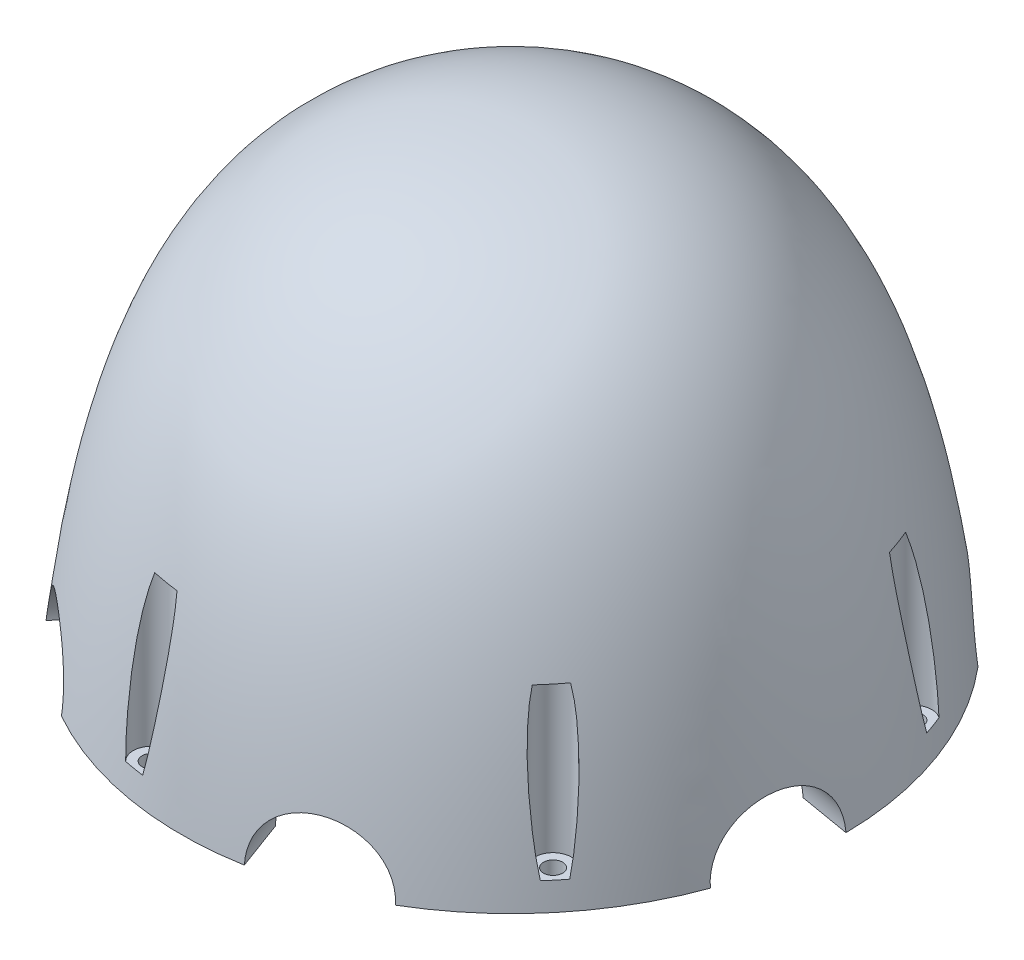
SolidWorks part; units mm, degrees
material "ABS"
ref_plane "前视基准面" through (0, 0, 0) normal (0, 0, 1) x (1, 0, 0)
ref_plane "上视基准面" through (0, 0, 0) normal (0, 1, 0) x (1, 0, 0)
ref_plane "右视基准面" through (0, 0, 0) normal (1, 0, 0) x (0, 0, -1)
sketch "草图1" plane through (0, 0, 0) normal (0, 0, 1) x (1, 0, 0)
  line L0 (-48.26, 0) -> (-57.15, 0)
  line L1 (0, 0) -> (0, 72.2657) construction
  line L2 (0, 72.2657) -> (0, 77.3457)
  line L3 (0, 77.3457) -> (27.4908, 77.3457) construction
  line L4 (0, 72.2657) -> (31.1413, 72.2657) construction
  spline S0 degree 3 poles (-48.26, 0) (-46.12, 40.7628) (-36.8511, 72.2657) (0, 72.2657) knots 0 0 0 0 1 1 1 1
  spline S1 degree 3 poles (-57.15, 0) (-53.2726, 34.209) (-44.696, 77.3457) (0, 77.3457) knots 0 0 0 0 1 1 1 1
  dimension "D3" = 5.08
  dimension "D1" = 114.3
  dimension "D2" = 8.89
revolve "旋转1" add sketch "草图1" angle 360 about L1
ref_plane "基准面1" through (0, 30.48, 0) normal (0, -1, 0) x (-1, 0, 0)
sketch "草图2" plane through (0, 30.48, 0) normal (0, -1, 0) x (-1, 0, 0)
  circle A0 centre (41.5481, 34.4537) radius 1.651
  circle A2 centre (50.6118, -18.7548) radius 1.651
  circle A3 centre (9.0637, -53.2085) radius 1.651
  circle A4 centre (-41.5481, -34.4537) radius 1.651
  circle A5 centre (-50.6118, 18.7548) radius 1.651
  circle A6 centre (-9.0637, 53.2085) radius 1.651
  point P17 (0, 0)
  dimension "D1" = 3.302
  dimension "D2" = 53.975
  dimension "D3" = 6
extrude "切除-拉伸2" cut sketch "草图2" along normal through all
sketch "草图3" plane through (0, 30.48, 0) normal (0, -1, 0) x (-1, 0, 0)
  circle A0 centre (41.5481, 34.4537) radius 3.175
  circle A2 centre (50.6118, -18.7548) radius 3.175
  circle A3 centre (9.0637, -53.2085) radius 3.175
  circle A4 centre (-41.5481, -34.4537) radius 3.175
  circle A6 centre (-50.6118, 18.7548) radius 3.175
  circle A7 centre (-9.0637, 53.2085) radius 3.175
  point P14 (16.2422, 43.8311)
  point P20 (0, 0)
  dimension "D1" = 6.35
  dimension "D2" = 53.975
  dimension "D3" = 6
extrude "切除-拉伸3" cut sketch "草图3" along normal blind 26
ref_axis "基准轴1" through (-50.6118, 4.48, 18.7548) along (0, 1, 0)
ref_axis "基准轴2" through (-41.5481, 4.48, -34.4537) along (0, 1, 0)
ref_plane "基准面2" through (-46.08, 0, -7.8494) normal (0.9858, 0, 0.1679) x (0.1679, 0, -0.9858)
ref_plane "基准面3" through (-78.6311, 0, -13.3943) normal (0.9858, 0, 0.1679) x (0.1679, 0, -0.9858)
sketch "草图4" plane through (-78.6311, 0, -13.3943) normal (0.9858, 0, 0.1679) x (0.1679, 0, -0.9858)
  line L0 (-57.15, 0) -> (57.15, 0) construction
  line L1 (10.16, 0) -> (-10.16, 0)
  arc A0 (10.16, 0) -> (-10.16, 0) centre (0, 0) ccw
  dimension "D1" = 10.16
extrude "切除-拉伸6" cut sketch "草图4" along normal through all
pattern_circular "阵列(圆周)1" count 3 over 360 about axis through (0, 0, 0) along (0, -1, 0) of "切除-拉伸6"
